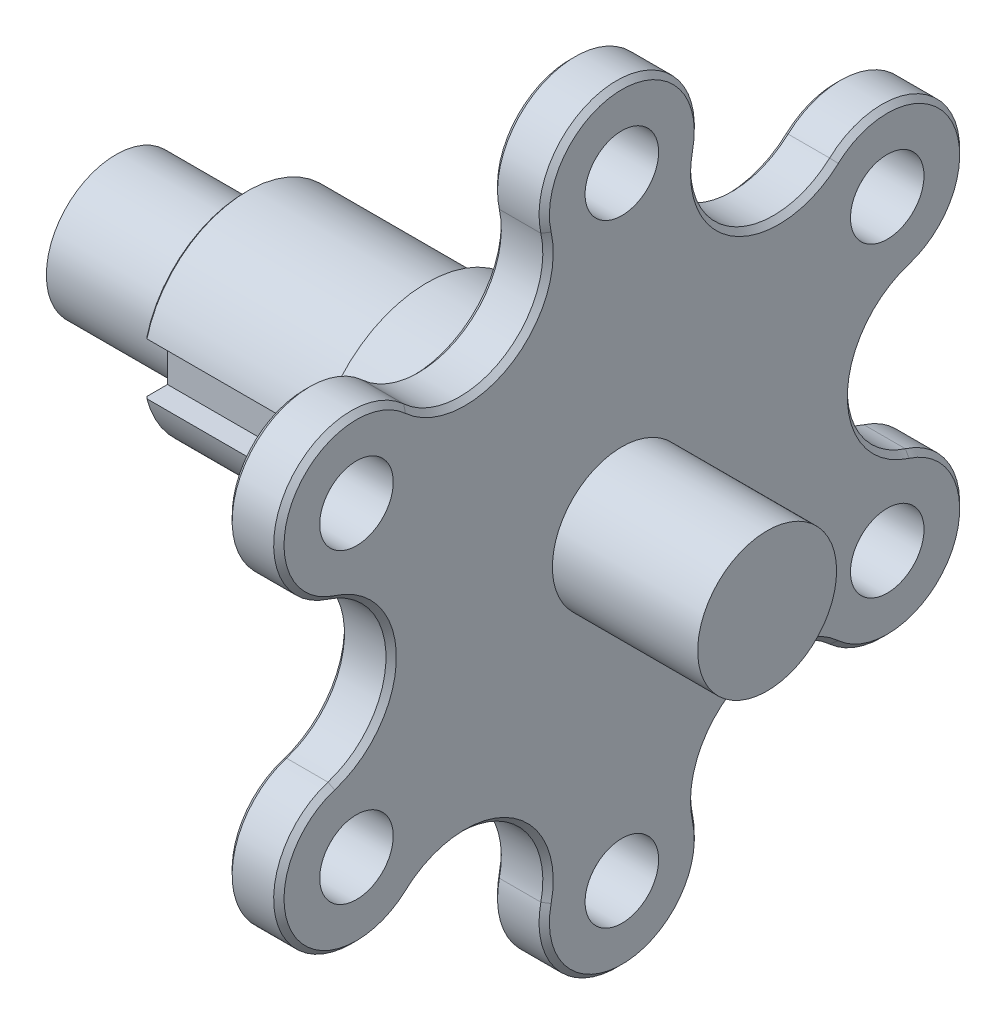
SolidWorks part; units mm, degrees
material "4140 Steel"
ref_plane "X-Y Datum" through (0, 0, 0) normal (0, 0, 1) x (1, 0, 0)
ref_plane "X-Z Datum" through (0, 0, 0) normal (0, 1, 0) x (1, 0, 0)
ref_plane "Y-Z Datum" through (0, 0, 0) normal (1, 0, 0) x (0, 0, -1)
sketch "Sketch1" plane through (0, 0, 0) normal (1, 0, 0) x (0, 0, -1)
  circle A0 centre (0, 0) radius 47
  dimension "D1" = 94
extrude "Base-Extrude" add sketch "Sketch1" against normal blind 6.35
hole_wizard "M8 Clearance Holes" positions "Sketch5" profile "Sketch7" hole size "M8" standard "ANSI Metric" end condition through all
sketch "Sketch5" plane through (0, 0, 0) normal (1, 0, 0) x (0, 0, -1)
  point P0 (0, -37.5)
  dimension "D1" = 37.5
sketch "Sketch7" plane through (0, -37.5, 0) normal (0, 1, 0) x (0, 0, -1)
  line L0 (0, 0) -> (0, 6.35)
  line L1 (0, 6.35) -> (4.5, 6.35)
  line L2 (4.5, 6.35) -> (4.5, 0)
  line L5 (4.5, 0) -> (0, 0)
  line L11 (0, -6.35) -> (0, 107.95) construction
  dimension "Thru Hole Dia." = 9
  dimension "Thru Hole Depth" = 6.35
pattern_circular "CirPattern" count 6 over 360 about axis through (-6.35, 0, 0) along (1, 0, 0) of "M8 Clearance Holes"
sketch "Sketch19" plane through (0, 0, 0) normal (1, 0, 0) x (0, 0, -1)
  line L0 (0, 37.5) -> (32.476, 18.75) construction
  circle A0 centre (0, 37.5) radius 9.5
  circle A1 centre (32.476, 18.75) radius 9.5
  circle A2 centre (0, 0) radius 47 construction
  arc A3 (9.2748, 35.4439) -> (26.0579, 25.7542) centre (19.194, 33.245) ccw
  circle A4 centre (32.476, 18.75) radius 9.5
  circle A5 centre (32.476, -18.75) radius 9.5
  arc A6 (35.3328, 9.6897) -> (35.3328, -9.6897) centre (38.3881, 0) ccw
  circle A7 centre (32.476, -18.75) radius 9.5
  circle A8 centre (0, -37.5) radius 9.5
  arc A9 (26.0579, -25.7542) -> (9.2748, -35.4439) centre (19.194, -33.245) ccw
  circle A10 centre (0, -37.5) radius 9.5
  circle A11 centre (-32.476, -18.75) radius 9.5
  arc A12 (-9.2748, -35.4439) -> (-26.0579, -25.7542) centre (-19.194, -33.245) ccw
  circle A13 centre (-32.476, -18.75) radius 9.5
  circle A14 centre (-32.476, 18.75) radius 9.5
  arc A15 (-35.3328, -9.6897) -> (-35.3328, 9.6897) centre (-38.3881, 0) ccw
  circle A16 centre (-32.476, 18.75) radius 9.5
  circle A17 centre (0, 37.5) radius 9.5
  arc A18 (-26.0579, 25.7542) -> (-9.2748, 35.4439) centre (-19.194, 33.245) ccw
  circle A19 centre (-32.476, 18.75) radius 4.5 construction
  circle M12 centre (0, 0) radius 47
  dimension "D1" = 10.16
  dimension "D2" = 6
extrude "Cut-Extrude" cut sketch "Sketch19" against normal through all both and the other way through all contours A16 A18 A0 M12 | A0 A3 A1 M12 | A13 A15 A14 M12 | A4 A6 A5 M12 | A7 A9 A8 M12 | A10 A12 A11 M12 | L0 A3 region at (0, 34.8675, -20.1307) region at (0, 26.6235, -15.3711) region at (0, 33.8688, 19.5541) region at (0, 0, -39.1083) region at (0, 0, 39.1083) region at (0, -33.8688, 19.5541) region at (0, -33.8688, -19.5541)
chamfer "Chamfer1" distance 0.635 angle 45 12 edges at (-6.35, 0, 28.2281) (-6.35, -23.5, 40.7032) (-6.35, 23.5, 40.7032) (-6.35, -24.4462, 14.114) (-6.35, 24.4462, 14.114) (-6.35, -47, 0) (-6.35, 47, 0) (-6.35, -24.4462, -14.114) (-6.35, -23.5, -40.7032) (-6.35, 0, -28.2281) (-6.35, 23.5, -40.7032) (-6.35, 24.4462, -14.114)
sketch "Sketch8" plane through (-6.35, 0, 0) normal (-1, 0, 0) x (0, 0, 1)
  circle A0 centre (0, 0) radius 12.7
  dimension "D1" = 25.4
extrude "Shaft-Extrude" add sketch "Sketch8" along normal blind 52.582
ref_plane "Plane2" through (-24, 0, 0) normal (-1, 0, 0) x (0, 0, 1)
sketch "Sketch44" plane through (0, 0, 0) normal (0, 1, 0) x (1, 0, 0)
  line L0 (25.0524, 0) -> (-95.9957, 0)
chamfer "Chamfer3" distance 0.635 angle 45 12 edges at (0, -23.5, 40.7032) (0, 0, 28.2281) (0, -24.4462, 14.114) (0, 23.5, 40.7032) (0, -47, 0) (0, 24.4462, 14.114) (0, -24.4462, -14.114) (0, 47, 0) (0, 24.4462, -14.114) (0, -23.5, -40.7032) (0, 0, -28.2281) (0, 23.5, -40.7032)
chamfer "Shaft Chamfer" distance 1 angle 45 1 edges at (-58.932, 0, 12.7)
sketch "Sketch22" [suppressed] plane through (-6.35, 0, 0) normal (-1, 0, 0) x (0, 0, 1)
  circle A0 centre (32.476, 18.75) radius 6.1
  circle A1 centre (32.476, -18.75) radius 6.1
  circle A2 centre (0, -37.5) radius 6.1
  circle A3 centre (0, 37.5) radius 6.1
  circle A4 centre (-32.476, 18.75) radius 6.1
  circle A5 centre (-32.476, -18.75) radius 6.1
  dimension "D1" = 12.2
split line "Split Line1" [suppressed]
split line "Split Line2"
sketch "Sketch22<2>" [suppressed] plane through (-6.35, 0, 0) normal (-1, 0, 0) x (0, 0, 1) same geometry as "Sketch22"
sketch "Sketch45" plane through (-58.932, 0, 0) normal (-1, 0, 0) x (0, 0, 1)
  circle A0 centre (0, 0) radius 12.7 construction
  circle A1 centre (0, 0) radius 12.7
  circle A2 centre (0, 0) radius 8.5127
  dimension "D1" = 17.0254
extrude "Cut-Extrude1" cut sketch "Sketch45" against normal blind 12.857
chamfer "Chamfer4" distance 0.254 angle 45 1 edges at (-46.075, 0, 12.7)
sketch "Sketch51" plane through (-6.35, 0, 0) normal (-1, 0, 0) x (0, 0, 1)
  circle A2 centre (0, 0) radius 13.97
  circle A3 centre (0, 0) radius 13.97
  dimension "D1" = 1.27
extrude "Boss-Extrude1" add sketch "Sketch51" along normal blind 17.5
fillet "Fillet4" radius 1.5875 1 edges at (-6.35, 0, -13.97)
ref_plane "Plane3" through (0, 0, 12.7) normal (0, 0, 1) x (1, 0, 0)
sketch "Sketch48" plane through (0, 0, 12.7) normal (0, 0, 1) x (1, 0, 0)
  line L0 (-46.075, 12.446) -> (-46.075, -12.446) construction
  line L1 (-23.85, 3.175) -> (-46.075, 3.175)
  line L3 (-23.85, -3.175) -> (-46.075, -3.175)
  line L4 (-46.075, 3.175) -> (-46.075, -3.175)
  line L5 (-46.075, 12.446) -> (-46.075, -12.446)
  line L6 (-46.075, 0) -> (-12.2887, 0) construction
  line L7 (-23.85, 12.7) -> (-23.85, -12.7) construction
  arc A0 (-23.85, 3.175) -> (-23.85, -3.175) centre (-23.85, 0) cw
  dimension "D2" = 6.35
extrude "Cut-Extrude3" cut sketch "Sketch48" against normal blind 3.175 and the other way blind 17.5 contours L4 L6 A0 L1 | L6 L5 L3 A0 region at (-33.7055, 1.5633, 12.7) region at (-33.7055, -1.5633, 12.7)
ref_plane "Plane4" through (0, 0, 13.97) normal (0, 0, 1) x (1, 0, 0)
fillet "Fillet5" radius 0.7937 1 edges at (-23.85, 0, -12.7)
sketch "Sketch55" plane through (0, 0, 0) normal (1, 0, 0) x (0, 0, -1)
  circle A0 centre (0, 0) radius 8.5
  dimension "D1" = 17
extrude "Boss-Extrude4" add sketch "Sketch55" along normal blind 17.78
sketch "Sketch56" plane through (-58.932, 0, 0) normal (-1, 0, 0) x (0, 0, 1)
  circle A1 centre (0, 0) radius 8.5127
  circle A2 centre (0, 0) radius 8.5127
  dimension "D1" = 0
extrude "Boss-Extrude5" add sketch "Sketch56" along normal blind 1.143
sketch "Sketch58" plane through (-60.075, 0, 0) normal (-1, 0, 0) x (0, 0, 1)
  circle A0 centre (0, 0) radius 8.5127
extrude "Boss-Extrude6" add sketch "Sketch58" along normal blind 1.8382
sketch "Sketch59" plane through (-61.9132, 0, 0) normal (-1, 0, 0) x (0, 0, 1)
  circle A0 centre (0, 0) radius 4.3656
  dimension "D1" = 8.7312
extrude "Cut-Extrude4" cut sketch "Sketch59" against normal blind 16.254
sketch "Sketch61" plane through (-46.075, 0, 0) normal (-1, 0, 0) x (0, 0, 1)
  line L0 (0, 0) -> (-12.7, 0) construction
  arc A0 (12.2967, 3.175) -> (12.2967, -3.175) centre (0, 0) ccw construction
  arc A1 (12.2967, 3.175) -> (12.2967, -3.175) centre (0, 0) ccw construction
  circle A3 centre (0, -12.7) radius 2.3813
  circle A4 centre (-12.7, 0) radius 2.3813
  dimension "D1" = 4.7625
extrude "Cut-Extrude5" cut sketch "Sketch61" against normal blind 25.4
